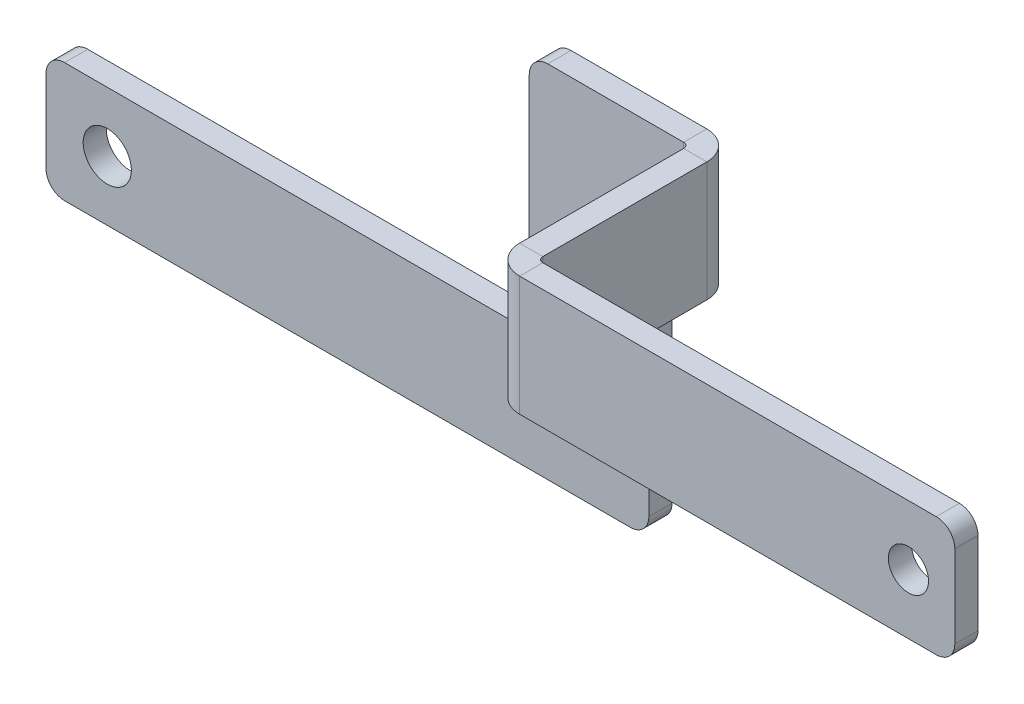
SolidWorks part; units mm, degrees
note: The reader was unsure of these and kept them because the rebuilt part matched: flange length of "Edge-Flange1", "Edge-Flange2".
material "3003-H14"
ref_plane "X-Y Datum" through (0, 0, 0) normal (0, 0, 1) x (1, 0, 0)
ref_plane "X-Z Datum" through (0, 0, 0) normal (0, 1, 0) x (1, 0, 0)
ref_plane "Y-Z Datum" through (0, 0, 0) normal (1, 0, 0) x (0, 0, -1)
sketch "Sketch1" plane through (0, 0, 0) normal (0, 0, 1) x (1, 0, 0)
  line L0 (-21.2828, -70.3126) -> (-12.741, -70.3126) construction
  line L5 (61.9125, -37.3736) -> (56.0244, -37.3736) construction
  line L9 (40.772, -29.1846) -> (40.772, -45.5626)
  line L10 (57.15, -45.5626) -> (61.9125, -45.5626)
  line L12 (40.772, -29.1846) -> (61.9125, -29.1846)
  line L13 (61.9125, -45.5626) -> (61.9125, -29.1846)
  line L14 (88.5359, -37.3736) -> (100.5639, -37.3736) construction
  line L15 (-25.4, -70.3126) -> (57.15, -70.3126) construction
  line L17 (57.15, -45.5626) -> (57.15, -78.5016)
  line L19 (40.772, -45.5626) -> (40.772, -62.1236)
  line L20 (57.15, -78.5016) -> (-25.4, -78.5016)
  line L22 (40.772, -62.1236) -> (-25.4, -62.1236)
  line L23 (-25.4, -78.5016) -> (-25.4, -62.1236)
  circle A0 centre (10, -8.189) radius 4 construction
  point P4 (-13.8233, -69.2831)
  point P9 (94.5499, -37.3736)
  point P19 (-17.0119, -70.3126)
  point P26 (94.5499, -37.3736)
  point P28 (-17.0119, -70.3126)
  dimension "D3" = 8
  dimension "D1" = 16.378
  dimension "D2" = 21.1405
  dimension "D4" = 16.378
  dimension "D5" = 82.55
  dimension "D6" = 16.378
base flange "Base-Flange1" sketch "Sketch1" thickness 3.175 reverse thickness direction no parameters "D1"=0.7366
edge flange "Edge-Flange1" sketch "Sketch12" flange angle 90 flange length 23.9268 flange position bend outside bend radius 0.7366 thickness 3.175 relief rectangular parameters "D6"=10
sketch "Sketch12" plane through (61.9125, 0, 0) normal (1, 0, 0) x (0, 1, 0)
  line L0 (-45.5626, 0) -> (-29.1846, 0) construction
  line L1 (-45.5626, 0) -> (-29.1846, 0)
  line L2 (-45.5626, 0) -> (-45.5626, 23.9268)
  line L3 (-45.5626, 23.9268) -> (-29.1846, 23.9268)
  line L4 (-29.1846, 23.9268) -> (-29.1846, 0)
bend "EdgeBend1" bend radius 0.7366 bend angle 90 parameters "D5"=1
edge flange "Edge-Flange2" sketch "Sketch15" flange angle 90 flange length 63.5 flange position material outside bend radius 0.7366 thickness 3.175 relief rectangular parameters "D6"=10
sketch "Sketch15" plane through (65.8241, 0, 23.9268) normal (0, 0, 1) x (0, -1, 0)
  line L0 (29.1846, 0) -> (45.5626, 0) construction
  line L1 (29.1846, 0) -> (45.5626, 0)
  line L2 (29.1846, 0) -> (29.1846, 60.325)
  line L3 (29.1846, 60.325) -> (45.5626, 60.325)
  line L4 (45.5626, 60.325) -> (45.5626, 0)
bend "EdgeBend2" bend radius 0.7366 bend angle 90 parameters "D5"=2
sketch "Sketch16" plane through (0, 0, 27.1018) normal (0, 0, 1) x (1, 0, 0)
  line L0 (126.1491, -37.3736) -> (91.3575, -37.3736) construction
  line L1 (126.1491, -45.5626) -> (126.1491, -29.1846) construction
  circle A0 centre (119.7991, -37.3736) radius 2.5 construction
  dimension "D1" = 5
  dimension "D2" = 6.35
hole_wizard "M5 Clearance Hole1" positions "Sketch17" profile "Sketch18" hole size "M5" standard "ANSI Metric" end condition through all
sketch "Sketch17" plane through (0, 0, 27.1018) normal (0, 0, 1) x (1, 0, 0)
  point P10 (119.7991, -37.3736)
sketch "Sketch18" plane through (119.7991, -37.3736, 27.1018) normal (1, 0, 0) x (0, -1, 0)
  line L0 (0, 0) -> (0, 30.2768)
  line L1 (0, 30.2768) -> (2.75, 30.2768)
  line L2 (2.75, 30.2768) -> (2.75, 0)
  line L5 (2.75, 0) -> (0, 0)
  line L11 (0, -6.35) -> (0, 107.95) construction
  dimension "Thru Hole Dia." = 5.5
  dimension "Thru Hole Depth" = 30.2768
hole_wizard "M6 Clearance Hole1" positions "Sketch19" profile "Sketch20" hole size "M6" standard "ANSI Metric" end condition through all
sketch "Sketch19" plane through (0, 0, 0) normal (0, 0, 1) x (1, 0, 0)
  point P5 (-17.0119, -70.3126)
  point P8 (-17.0119, -70.3126)
sketch "Sketch20" plane through (-17.0119, -70.3126, 0) normal (1, 0, 0) x (0, -1, 0)
  line L0 (0, 0) -> (0, 3.175)
  line L1 (0, 3.175) -> (3.3, 3.175)
  line L2 (3.3, 3.175) -> (3.3, 0)
  line L5 (3.3, 0) -> (0, 0)
  line L11 (0, -6.35) -> (0, 107.95) construction
  dimension "Thru Hole Dia." = 6.6
  dimension "Thru Hole Depth" = 3.175
fillet "Fillet1" radius 2.54 8 edges at (-25.4, -78.5016, -1.5875) (-25.4, -62.1236, -1.5875) (40.772, -62.1236, -1.5875) (57.15, -78.5016, -1.5875) (57.15, -45.5626, -1.5875) (40.772, -29.1846, -1.5875) (126.1491, -45.5626, 25.5143) (126.1491, -29.1846, 25.5143)
sketch "Bend-Lines1" [suppressed] plane through (0, 0, 0) normal (0, 1, 0) x (1, 0, 0)
sketch "Bounding-Box1" [suppressed] plane through (0, 0, 0) normal (0, 1, 0) x (1, 0, 0)
sheet metal parameters "Sheet-Metal3" thickness 3.175 parameters "D1"=0.7366
flat pattern "Flat-Pattern3" [suppressed]
sketch "Bend-Lines2" plane through (0, 0, 0) normal (0, 1, 0) x (1, 0, 0)
sketch3d "Bounding-Box2" [suppressed]
  line L0 (0, -16.378, 0) -> (-76.2, -16.378, 0) construction
  line L1 (0, 0, 0) -> (-76.2, 0, 0) construction
  line L2 (0, -16.378, 0) -> (0, 0, 0) construction
  line L3 (-76.2, -16.378, 0) -> (-76.2, 0, 0) construction
sheet metal parameters "Sheet-Metal5" thickness 3.175 parameters "D1"=0.7366
flat pattern "Flat-Pattern3"
sketch "Bend-Lines2" plane through (0, 0, 0) normal (0, 0, 1) x (1, 0, 0)
  line L0 (62.1503, -45.5626) -> (62.1503, -29.1846) construction
  line L1 (62.1503, -45.5626) -> (62.1503, -29.1846) construction
sketch3d "Bounding-Box2" [suppressed]
  line L0 (0, -45.5626, 0) -> (87.1659, -45.5626, 0) construction
  line L1 (0, 0, 0) -> (87.1659, 0, 0) construction
  line L2 (0, -45.5626, 0) -> (0, 0, 0) construction
  line L3 (87.1659, -45.5626, 0) -> (87.1659, 0, 0) construction
bend of the flat pattern "Flatten-<EdgeBend1>1"
sheet metal parameters "Sheet-Metal6" thickness 3.175 parameters "D1"=0.7366
flat pattern "Flat-Pattern3"
sketch "Bend-Lines2" plane through (0, 0, 0) normal (0, 0, 1) x (1, 0, 0)
  line L0 (62.1503, -45.5626) -> (62.1503, -29.1846) construction
  line L1 (62.1503, -45.5626) -> (62.1503, -29.1846) construction
  line L2 (88.2546, -45.5626) -> (88.2546, -29.1846) construction
  line L3 (88.2546, -45.5626) -> (88.2546, -29.1846) construction
sketch3d "Bounding-Box2" [suppressed]
  line L0 (0, -45.5626, 0) -> (125.5384, -45.5626, 0) construction
  line L1 (0, 0, 0) -> (125.5384, 0, 0) construction
  line L2 (0, -45.5626, 0) -> (0, 0, 0) construction
  line L3 (125.5384, -45.5626, 0) -> (125.5384, 0, 0) construction
bend of the flat pattern "Flatten-<EdgeBend1>1"
bend of the flat pattern "Flatten-<EdgeBend2>1"
sheet metal parameters "Sheet-Metal7" thickness 3.175 parameters "D1"=0.7366
flat pattern "Flat-Pattern3" [suppressed]
sketch "Bend-Lines2" plane through (0, 0, 0) normal (0, 0, 1) x (1, 0, 0)
  line L0 (63.7378, -45.5626) -> (63.7378, -29.1846) construction
  line L1 (63.7378, -45.5626) -> (63.7378, -29.1846) construction
  line L2 (89.8421, -45.5626) -> (89.8421, -29.1846) construction
  line L3 (89.8421, -45.5626) -> (89.8421, -29.1846) construction
sketch3d "Bounding-Box2" [suppressed]
  line L0 (-19.553, -77.3126, 0) -> (151.2559, -77.3126, 0) construction
  line L1 (-19.553, -29.1846, 0) -> (151.2559, -29.1846, 0) construction
  line L2 (-19.553, -77.3126, 0) -> (-19.553, -29.1846, 0) construction
  line L3 (151.2559, -77.3126, 0) -> (151.2559, -29.1846, 0) construction
bend of the flat pattern "Flatten-<EdgeBend1>1"
bend of the flat pattern "Flatten-<EdgeBend2>1"
sketch "Sketch16-1" [suppressed] plane through (25.1068, 0, 0) normal (0, 0, 1) x (1, 0, 0)
  line L0 (126.1491, -37.3736) -> (91.3575, -37.3736) construction
  line L1 (126.1491, -45.5626) -> (126.1491, -29.1846) construction
  circle A0 centre (119.7991, -37.3736) radius 2.5 construction
  dimension "D1" = 5
  dimension "D2" = 6.35
sheet metal parameters "Sheet-Metal8" thickness 3.175 parameters "D1"=0.7366
flat pattern "Flat-Pattern3" [suppressed]
sketch "Bend-Lines2" plane through (0, 0, 0) normal (0, 0, 1) x (1, 0, 0)
  line L0 (63.7378, -45.5626) -> (63.7378, -29.1846) construction
  line L1 (63.7378, -45.5626) -> (63.7378, -29.1846) construction
  line L2 (89.8421, -45.5626) -> (89.8421, -29.1846) construction
  line L3 (89.8421, -45.5626) -> (89.8421, -29.1846) construction
sketch3d "Bounding-Box2" [suppressed]
  line L0 (-25.4, -78.5016, 0) -> (151.2559, -78.5016, 0) construction
  line L1 (-25.4, -29.1846, 0) -> (151.2559, -29.1846, 0) construction
  line L2 (-25.4, -78.5016, 0) -> (-25.4, -29.1846, 0) construction
  line L3 (151.2559, -78.5016, 0) -> (151.2559, -29.1846, 0) construction
bend of the flat pattern "Flatten-<EdgeBend1>1"
bend of the flat pattern "Flatten-<EdgeBend2>1"
sketch "Sketch16-1" plane through (25.1068, 0, 0) normal (0, 0, 1) x (1, 0, 0)
  line L0 (126.1491, -37.3736) -> (91.3575, -37.3736) construction
  line L1 (126.1491, -43.0226) -> (126.1491, -31.7246) construction
  circle A0 centre (119.7991, -37.3736) radius 2.5 construction
  dimension "D1" = 5
  dimension "D2" = 6.35
